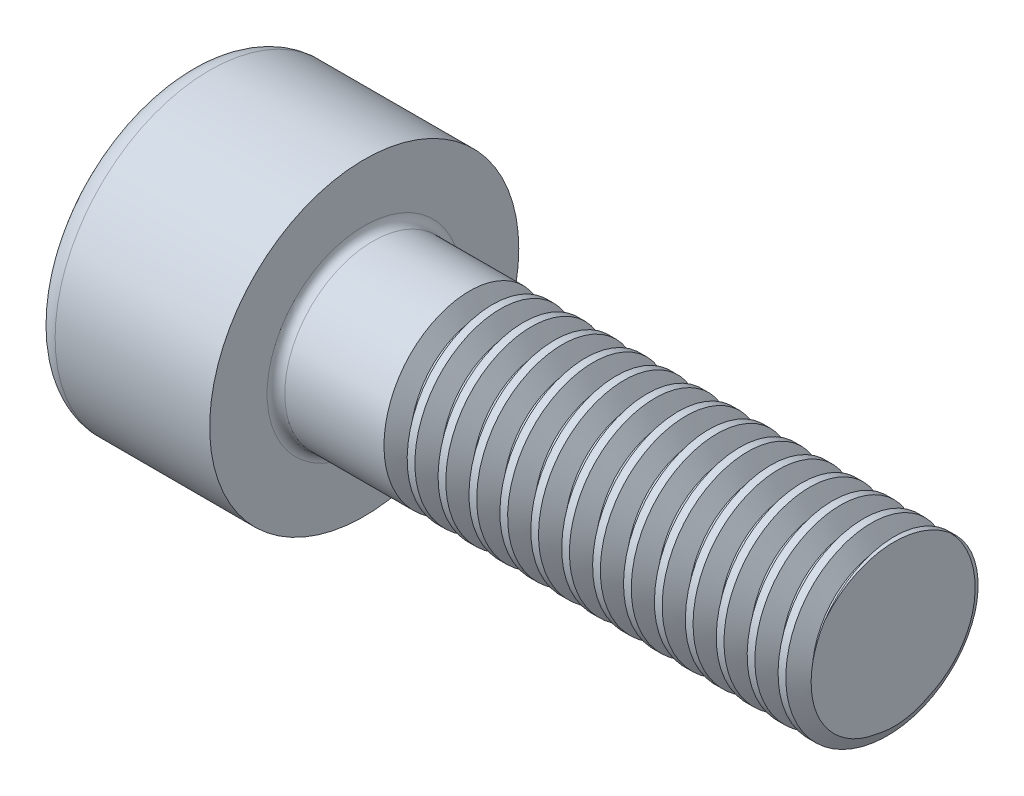
SolidWorks part; units mm, degrees
ref_plane "Спереди" through (0, 0, 0) normal (0, 0, 1) x (1, 0, 0)
ref_plane "Сверху" through (0, 0, 0) normal (0, 1, 0) x (1, 0, 0)
ref_plane "Справа" through (0, 0, 0) normal (1, 0, 0) x (0, 0, -1)
sketch "Эскиз1" plane through (0, 0, 0) normal (0, 0, 1) x (1, 0, 0)
  line L0 (22.1989, 0) -> (16, 0) construction
  line L1 (0, 16.1035) -> (0, -19.7496) construction
  line L2 (0, 0) -> (16, 0)
  line L3 (0, 0) -> (0, 3.5)
  line L4 (0, 3.5) -> (4, 3.5)
  line L5 (4, 3.5) -> (4, 2)
  line L6 (4, 2) -> (16, 2)
  line L7 (16, 2) -> (16, 0)
  point P2 (0, 0)
  point P7 (0, 0)
  point P8 (8, 0)
  point P13 (0, 0)
  point P14 (11.0203, 0)
  point P15 (0, 0)
  point P16 (22.1989, 0)
  dimension "D1" = 7
  dimension "D2" = 4
  dimension "D3" = 12
  dimension "D4" = 4
revolve "Повернуть1" add sketch "Эскиз1" angle 360 about L0
thread "Резьба1" pitch 0.7 method cut profile "Профиль резьбы2" start angle 0, offset 2.1, length 0, pitch 0.7, diameter 4
ref_plane "Плоскость2" through (6.1, 0, -2) normal (0, 1, 0) x (0, 0, 1)
sketch "Профиль резьбы2" plane through (6.1, 0, -2) normal (0, 1, 0) x (0, 0, 1)
  line L0 (0, 0) -> (0, 0.7) construction
  line L1 (0, 0) -> (0.3789, 0.2187)
  line L2 (0.3789, 0.2187) -> (0.3789, 0.3062)
  line L3 (0.3789, 0.3062) -> (0, 0.525)
  line L4 (0.3789, 0.2625) -> (0, 0.2625) construction
  line L11 (0, 0) -> (0, 0.525)
  point P2 (0, 0)
  dimension "Pitch" = 0.7
  dimension "Profile_Angle" = 60
  dimension "Profile_Land" = 0.0875
  dimension "Profile_Height" = 0.3789
sketch "Эскиз6" plane through (0, 0, 0) normal (-1, 0, 0) x (0, 0, 1)
  line L0 (0, 0) -> (-5.0338, 0) construction
  line L1 (0, 0) -> (0, 5.5177) construction
  line L3 (-1.72, 0) -> (-0.86, -1.4896)
  line L4 (-0.86, -1.4896) -> (0.86, -1.4896)
  line L5 (0.86, -1.4896) -> (1.72, 0)
  line L6 (1.72, 0) -> (0.86, 1.4896)
  line L7 (0.86, 1.4896) -> (-0.86, 1.4896)
  line L8 (-0.86, 1.4896) -> (-1.72, 0)
  point P3 (0, 0)
  dimension "D1" = 2.9792
  dimension "D2" = 3.44
extrude "Вырез-Вытянуть1" cut sketch "Эскиз6" against normal blind 2 contours L3 L4 L5 L6 L7 L8
extrude "Вырез-Вытянуть2" cut sketch "Эскиз6<3>" against normal blind 2 draft 60 from offset 2 offset against normal yes
sketch "Эскиз6<3>" plane through (0, 0, 0) normal (-1, 0, 0) x (0, 0, 1) same geometry as "Эскиз6"
fillet "Скругление2" radius 0.5 1 edges at (0, 0, -3.5)
fillet "Скругление3" radius 0.2 1 edges at (4, 0, -2)
